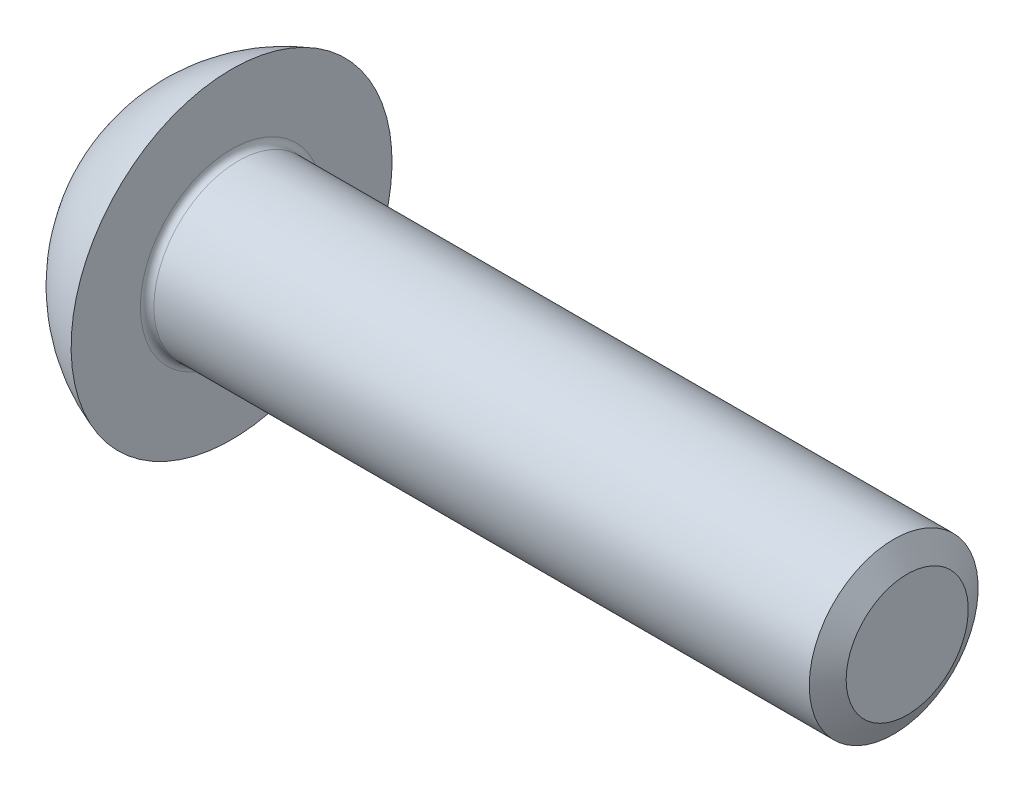
SolidWorks part; units mm, degrees
ref_plane "前视基准面" through (0, 0, 0) normal (0, 0, 1) x (1, 0, 0)
ref_plane "上视基准面" through (0, 0, 0) normal (0, 1, 0) x (1, 0, 0)
ref_plane "右视基准面" through (0, 0, 0) normal (1, 0, 0) x (0, 0, -1)
sketch "草图1" plane through (0, 0, 0) normal (0, 0, 1) x (1, 0, 0)
  line L0 (-22.75, 0) -> (0, 0) construction
  line L1 (0, 2.5) -> (-19.8, 2.5)
  line L2 (-20, 2.7) -> (-20, 4.75)
  line L3 (-22.75, 0) -> (-22.75, 2.5)
  line L4 (0, 2.5) -> (0, 0)
  line L5 (-22.75, 0) -> (0, 0)
  arc A0 (-20, 4.75) -> (-22.75, 2.5) centre (-18.4091, 0) ccw
  arc A1 (-19.8, 2.5) -> (-20, 2.7) centre (-19.8, 2.7) cw
  point P10 (-20, 2.5)
  dimension "r" = 0.2
  dimension "d" = 5
  dimension "dk" = 9.5
  dimension "k" = 2.75
  dimension "l" = 20
revolve "旋转1" add sketch "草图1" angle 360 about L0
cosmetic thread "装饰螺纹线1" parameters "D1"=2, "D2"=4.3
sketch "草图2" plane through (-22.75, 0, 0) normal (-1, 0, 0) x (0, 0, 1)
  line L1 (0, 1.7321) -> (-1.5, 0.866)
  line L2 (-1.5, 0.866) -> (-1.5, -0.866)
  line L3 (-1.5, -0.866) -> (0, -1.7321)
  line L4 (0, -1.7321) -> (1.5, -0.866)
  line L5 (1.5, -0.866) -> (1.5, 0.866)
  line L6 (1.5, 0.866) -> (0, 1.7321)
  circle A0 centre (0, 0) radius 1.5 construction
  dimension "s" = 3
extrude "切除-拉伸1" cut sketch "草图2" against normal blind 2.75
sketch "草图6" plane through (0, 0, 0) normal (0, 0, 1) x (1, 0, 0)
  line L0 (-21.19, 1.7321) -> (-20, 0)
  line L1 (-19.56, 1.7321) -> (-19.56, 0)
  line L2 (-19.56, 1.7321) -> (-21.19, 1.7321)
  line L3 (-22.75, 0) -> (-20, 0) construction
  line L4 (-19.56, 0) -> (-20, 0)
  line L5 (-22.75, 0) -> (-26.19, 0) construction
  dimension "k" = 2.75
  dimension "t" = 1.56
  dimension "e-s" = 0.44
  dimension "e" = 3.44
revolve "旋转2" add sketch "草图6" angle 360 about L3
sketch "草图7" plane through (0, 0, 0) normal (0, 0, 1) x (1, 0, 0)
  line L3 (-22.75, 1.7321) -> (-22.31, 0)
  line L4 (-22.75, 0) -> (-22.31, 0) construction
  line L7 (-22.75, 1.7321) -> (-22.75, 0)
  line L8 (-22.75, 0) -> (-22.31, 0)
  dimension "e-s" = 0.44
revolve "切除-旋转5" cut sketch "草图7" angle 360 about L4
sketch "草图4" plane through (0, 0, 0) normal (0, 0, 1) x (1, 0, 0)
  line L0 (-0.4, 2.5) -> (0, 1.8072)
  line L1 (-0.4, 2.5) -> (0.4, 2.5)
  line L2 (0.4, 2.5) -> (0, 1.8072)
  line L4 (0, -2.5) -> (0, 2.5) construction
  line L5 (-0.4, 0) -> (0.4, 0) construction
  dimension "d" = 2.5
  dimension "p" = 0.8
revolve "切除-旋转1" cut sketch "草图4" angle 360 about L5
ref_axis "基准轴1" through (-8.1887, 0, 0) along (1, 0, 0)
pattern_linear "阵列(线性)1" [suppressed] count 3 spacing 0.8 along (-1, 0, 0) of bodies 104
equation "\"D2@装饰螺纹线1\" = \"d@草图1\" * 0.86"
equation "\"k@草图6\" = \"k@切除-拉伸1\""
equation "\"e-s@草图6\" = \"e@草图6\" - \"s@草图2\""
equation "\"e-s@草图7\" = \"e-s@草图6\""
equation "\"d@草图4\" = \"d@草图1\" / 2"
equation "\"k@切除-拉伸1\" = \"k@草图1\""
equation "\"D1@阵列(线性)1\" = \"D1@装饰螺纹线1\" / \"p@草图4\""
equation "\"D3@阵列(线性)1\" = \"p@草图4\""
